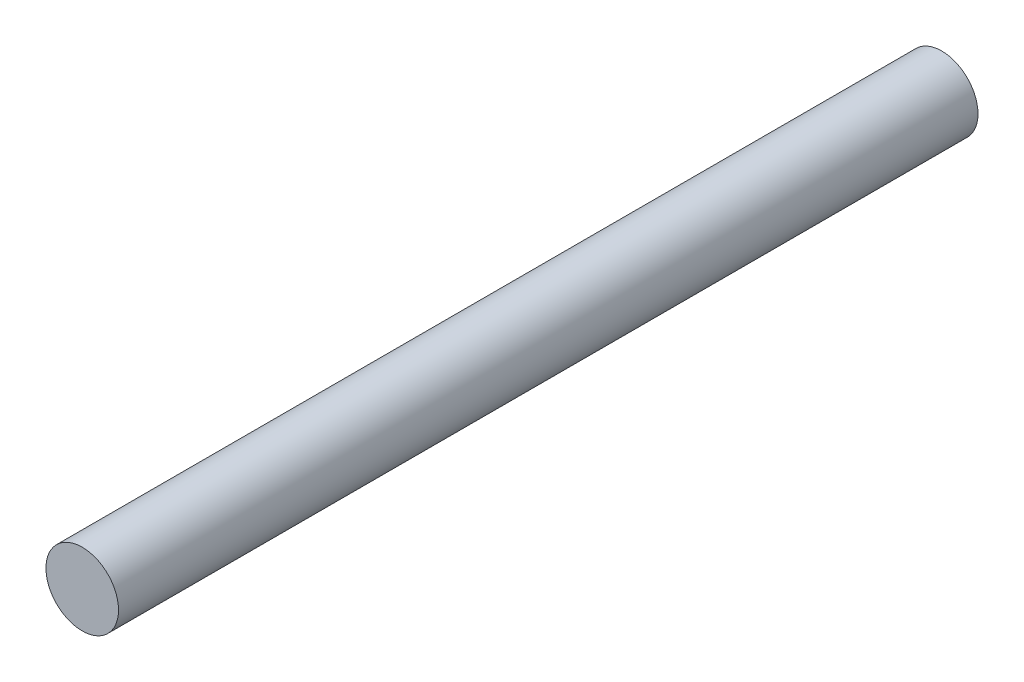
SolidWorks part; units mm, degrees
material "AISI 1020 Steel, Cold Rolled"
ref_plane "Front Plane" through (0, 0, 0) normal (0, 0, 1) x (1, 0, 0)
ref_plane "Top Plane" through (0, 0, 0) normal (0, 1, 0) x (1, 0, 0)
ref_plane "Right Plane" through (0, 0, 0) normal (1, 0, 0) x (0, 0, -1)
sketch "Sketch2" plane through (0, 0, 0) normal (0, 0, 1) x (1, 0, 0)
  circle A0 centre (0, 0) radius 7.9375
  dimension "D1" = 15.875
extrude "Boss-Extrude1" add sketch "Sketch2" along normal blind 187.96
sketch "Sketch3" [suppressed] plane through (0, 0, 220.98) normal (0, 0, 1) x (1, 0, 0)
  circle A0 centre (0, 0) radius 6.35
extrude "Cut-Extrude1" [suppressed] cut sketch "Sketch3" against normal blind 26.416
sketch "Sketch4" [suppressed] plane through (0, 0, 194.564) normal (0, 0, 1) x (1, 0, 0)
  circle A0 centre (0, 0) radius 3.175
  dimension "D1" = 6.35
extrude "Boss-Extrude2" [suppressed] add sketch "Sketch4" along normal blind 26.416
sketch "Sketch5" [suppressed] plane through (0, 0, 0) normal (0, 0, -1) x (-1, 0, 0)
  circle A0 centre (0, 0) radius 6.35
extrude "Cut-Extrude2" [suppressed] cut sketch "Sketch5" against normal blind 26.416
sketch "Sketch6" [suppressed] plane through (0, 0, 26.416) normal (0, 0, -1) x (-1, 0, 0)
  circle A0 centre (0, 0) radius 3.175
  dimension "D1" = 6.35
extrude "Boss-Extrude3" [suppressed] add sketch "Sketch6" along normal blind 26.416
sketch "Sketch7" [suppressed] plane through (0, 0, 0) normal (0, 0, -1) x (-1, 0, 0)
  circle A0 centre (0, 0) radius 14.231
extrude "Cut-Extrude3" [suppressed] cut sketch "Sketch7" against normal blind 27.432
sketch "Sketch8" [suppressed] plane through (0, 0, 27.432) normal (0, 0, -1) x (-1, 0, 0)
  circle A0 centre (0, 0) radius 3.175
  dimension "D1" = 6.35
extrude "Boss-Extrude4" [suppressed] add sketch "Sketch8" along normal blind 27.432
sketch "Sketch9" [suppressed] plane through (0, 0, 220.98) normal (0, 0, 1) x (1, 0, 0)
  circle A0 centre (0, 0) radius 8.8374
extrude "Cut-Extrude4" [suppressed] cut sketch "Sketch9" against normal blind 27.432
sketch "Sketch10" [suppressed] plane through (0, 0, 193.548) normal (0, 0, 1) x (1, 0, 0)
  circle A0 centre (0, 0) radius 3.175
  dimension "D1" = 6.35
extrude "Boss-Extrude5" [suppressed] add sketch "Sketch10" along normal blind 27.432
